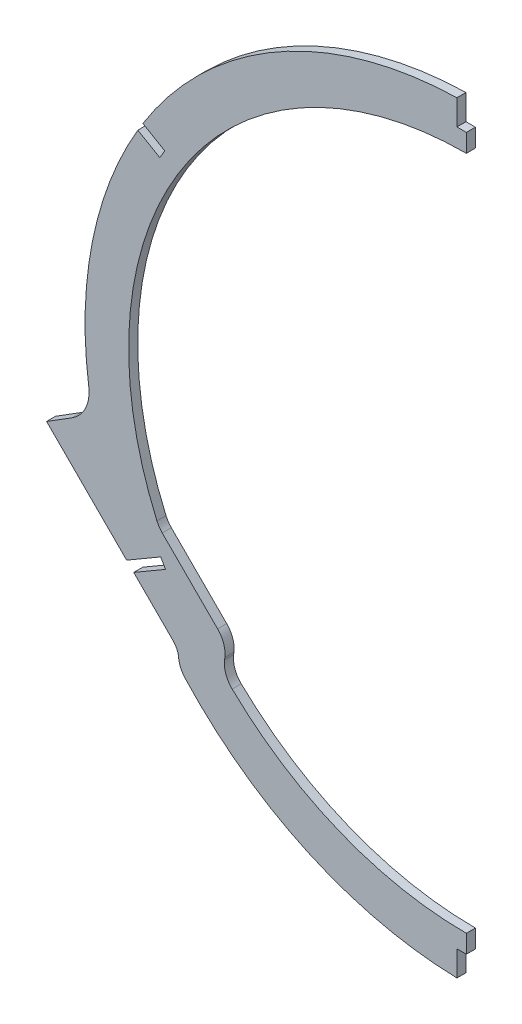
SolidWorks part; units mm, degrees
material "Plywood"
ref_plane "Front Plane" through (0, 0, 0) normal (0, 0, 1) x (1, 0, 0)
ref_plane "Top Plane" through (0, 0, 0) normal (0, 1, 0) x (1, 0, 0)
ref_plane "Right Plane" through (0, 0, 0) normal (1, 0, 0) x (0, 0, -1)
sketch "Sketch1" plane through (0, 0, 0) normal (0, 0, 1) x (1, 0, 0)
  line L0 (0, -110.0909) -> (0, -70.6286) construction
  line L2 (0, 0) -> (0, 631.6453) construction
  line L3 (-120.188, -34.2725) -> (-99.9824, -54.478)
  line L4 (0, 0) -> (-284.8905, 0) construction
  line L5 (-99.9824, -54.478) -> (-101.1426, -63.4095)
  line L8 (-99.9824, -54.478) -> (-57.7675, -96.693) construction
  line L9 (-99.9824, -54.478) -> (0, 0) construction
  line L10 (-101.1426, -63.4095) -> (0, 0) construction
  arc A0 (-57.7675, -96.693) -> (-120.188, -34.2725) centre (0, 23.495) ccw
  arc A2 (-120.188, -34.2725) -> (-57.7675, -96.693) centre (0, 23.495) ccw construction
  arc A3 (-101.1426, -63.4095) -> (-57.7675, -96.693) centre (0, 23.495) ccw
  point P2 (0, 156.7839)
  point P3 (0, -109.8059)
  point P15 (-99.9824, -54.478)
  dimension "D1" = 266.5898
  dimension "D2" = 266.7
  dimension "D3" = 23.495
  dimension "D5" = 109.22
  dimension "D6" = 45
  dimension "D7" = 28.575
  dimension "D4" = 3.5
extrude "Boss-Extrude1" add sketch "Sketch1" along normal mid plane 3.175
sketch "Sketch2" plane through (0, 0, 1.5875) normal (0, 0, 1) x (1, 0, 0)
  line L4 (-83.9033, -49.0045) -> (-85.1218, -58.3845)
  line L5 (-107.5191, -25.3887) -> (-83.9033, -49.0045)
  line L6 (-83.9033, -49.0045) -> (-85.1218, -58.3845)
  line L7 (-107.5191, -25.3887) -> (-83.9033, -49.0045)
  arc A2 (-85.1218, -58.3845) -> (-107.5191, -25.3887) centre (0, 23.495) ccw
  arc A3 (-85.1218, -58.3845) -> (-107.5191, -25.3887) centre (0, 23.495) ccw
  dimension "D1" = 15.24
extrude "Cut-Extrude1" cut sketch "Sketch2" against normal up to surface (3.175 mm away) up to face at (-33.0092, -2.288, -1.5875)
fillet "Fillet1" radius 8.89 6 edges at (-107.5191, -25.3887, 0) (-120.188, -34.2725, 0) (-101.1426, -63.4095, 0) (-99.9824, -54.478, 0) (-83.9033, -49.0045, 0) (-85.1218, -58.3845, 0)
sketch "Sketch3" plane through (0, 0, 0) normal (1, 0, 0) x (0, 0, -1)
  line L1 (-107.0531, 227.715) -> (127.3903, 227.715)
  line L2 (-107.0531, 227.715) -> (-107.0531, -194.8481)
  line L3 (-107.0531, -194.8481) -> (127.3903, -194.8481)
  line L4 (127.3903, 227.715) -> (127.3903, -194.8481)
extrude "Cut-Extrude2" cut sketch "Sketch3" along normal through all
sketch "Sketch5" plane through (0, 0, 0) normal (0, 0, 1) x (1, 0, 0)
  line L0 (-146.8166, -13.0034) -> (-125.2935, 0.4458)
  line L1 (-146.8166, -13.0034) -> (-100.6004, -59.2359)
  line L2 (0, 0) -> (-240.0313, 0) construction
  line L3 (-100.6004, -59.2359) -> (-91.9691, -50.6076)
  line L4 (-91.9691, -50.6076) -> (-125.2935, 0.4458)
  ellipse E0 centre (0.6289, 30.2513) end of major axis (130.0331, 30.2513) minor radius 129.3587 (-127.7603, 14.0811) -> (-84.313, -67.3377) ccw construction
  dimension "D1" = 45.01
  dimension "D2" = 113.0265
  dimension "D3" = 116.7447
  dimension "D4" = 32
  dimension "D5" = 65.3711
extrude "Boss-Extrude2" add sketch "Sketch5" along normal mid plane 3.175
fillet "Fillet2" radius 6.35 1 edges at (-100.6004, -59.2359, 0)
fillet "Fillet3" radius 12.7 1 edges at (-130.7045, -2.9354, 0)
sketch "Sketch6" plane through (0, 0, -1.5875) normal (0, 0, -1) x (-1, 0, 0)
  line L0 (0, 0) -> (0, 141.605) construction
  line L1 (0, 141.605) -> (0, 147.955) construction
  line L2 (0, 141.605) -> (0, 156.845) construction
  line L3 (0, 147.955) -> (3.302, 147.955)
  line L4 (0, 147.955) -> (0, 160.655)
  line L5 (3.302, 147.955) -> (3.302, 160.655)
  line L6 (0, 160.655) -> (3.302, 160.655)
  line L7 (100.8525, 84.9665) -> (106.3397, 88.1623) construction
  line L11 (105.4896, 89.6219) -> (107.1898, 86.7027)
  line L12 (100.8525, 84.9665) -> (0, 26.2278) construction
  line L13 (105.4896, 89.6219) -> (116.464, 96.0136)
  line L14 (107.1898, 86.7027) -> (118.1641, 93.0944)
  line L15 (116.464, 96.0136) -> (118.1641, 93.0944)
  line L23 (100.5646, -32.3432) -> (106.0518, -35.539) construction
  line L24 (0, 26.2278) -> (100.5646, -32.3432) construction
  line L25 (105.2017, -36.9986) -> (106.9019, -34.0795)
  line L26 (105.2017, -36.9986) -> (127.1504, -49.782)
  line L27 (106.9019, -34.0795) -> (128.8505, -46.8628)
  line L28 (127.1504, -49.782) -> (128.8505, -46.8628)
  line L29 (0, 26.2278) -> (0, -94.615) construction
  line L30 (0, -94.615) -> (0, -100.965) construction
  line L31 (0, -109.855) -> (0, -94.615) construction
  line L32 (0, -100.965) -> (3.302, -100.965)
  line L33 (0, -100.965) -> (0, -113.665)
  line L34 (3.302, -100.965) -> (3.302, -113.665)
  line L35 (0, -113.665) -> (3.302, -113.665)
  point P4 (106.3397, 88.1623)
  point P14 (106.0518, -35.539)
  point P21 (128.0005, -48.3224)
  dimension "D1" = 141.605
  dimension "D2" = 6.35
  dimension "D3" = 3.302
  dimension "D4" = 12.7
  dimension "D5" = 59.783
  dimension "D6" = 26.2278
  dimension "D7" = 116.711
  dimension "D8" = 6.35
  dimension "D9" = 12.7
  dimension "D10" = 3.3782
  dimension "D11" = 59.783
  dimension "D12" = 116.3778
  dimension "D13" = 6.35
  dimension "D14" = 3.3782
  dimension "D15" = 25.4
  dimension "D16" = 120.8428
  dimension "D17" = 6.35
  dimension "D18" = 3.302
  dimension "D19" = 12.7
extrude "Cut-Extrude3" cut sketch "Sketch6" against normal through all
